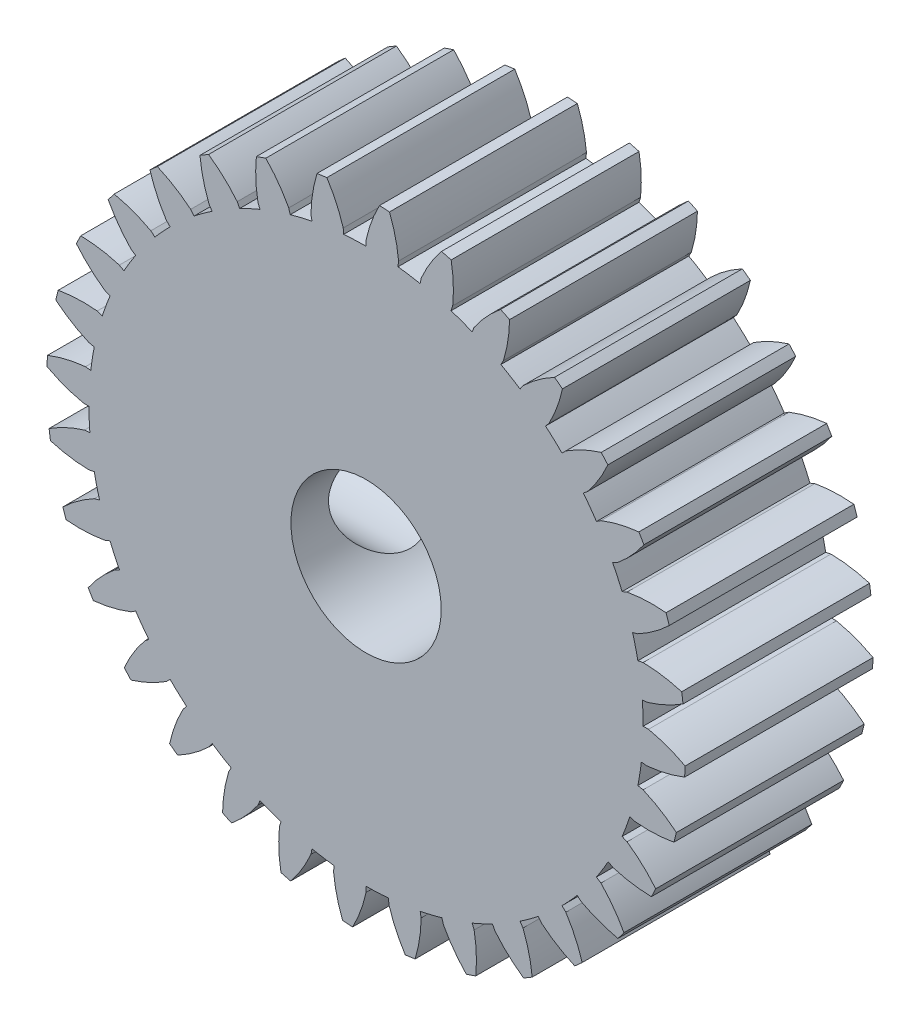
SolidWorks part; units mm, degrees
ref_plane "Front Plane" through (0, 0, 0) normal (0, 0, 1) x (1, 0, 0)
ref_plane "Top Plane" through (0, 0, 0) normal (0, 1, 0) x (1, 0, 0)
ref_plane "Right Plane" through (0, 0, 0) normal (1, 0, 0) x (0, 0, -1)
sketch "Gear" plane through (0, 0, 0) normal (0, 0, 1) x (1, 0, 0)
  circle A0 centre (0, 0) radius 8
  circle A1 centre (0, 0) radius 8.5
  circle A2 centre (0, 0) radius 7.375
  circle A3 centre (0, 0) radius 7.5
  circle A4 centre (0, 0) radius 7.5175
  dimension "Pitch" = 16
  dimension "Addendum" = 17
  dimension "Root" = 14.75
  dimension "Clearance" = 15
  dimension "Base" = 15.0351
sketch "Involute" plane through (0, 0, 0) normal (0, 0, 1) x (1, 0, 0)
  line L0 (0, 0) -> (0, 7.5175)
  line L1 (0, 0) -> (3.7588, 6.5104) construction
  line L2 (0, 0) -> (6.5104, 3.7588) construction
  line L3 (0, 0) -> (7.5175, 0) construction
  line L4 (7.5175, 0) -> (7.5175, 11.8085) construction
  line L5 (6.5104, 3.7588) -> (2.5742, 10.5764) construction
  line L6 (3.7588, 6.5104) -> (0.3499, 8.4785) construction
  line L7 (0, 0) -> (0.7841, 7.9615) construction
  line L8 (0, 0) -> (1.5607, 7.8463)
  line L9 (0.4614, 7.9867) -> (0, 0) construction
  circle A0 centre (0, 0) radius 7.5175 construction
  circle A1 centre (0, 0) radius 8 construction
  arc A3 (0.7841, 7.9615) -> (0.1378, 7.9988) centre (0, 0) ccw
  spline S0 degree 3 poles (0, 7.5175) (0.6613, 10.5961) (4.9807, 11.8125) (7.5175, 11.8085) knots 0 0 0 0 1 1 1 1
  spline S1 degree 3 poles (0.8656, 7.4675) (0.5632, 10.6018) (-3.5874, 12.3075) (-6.1078, 12.5956) knots 0 0 0 0 1 1 1 1
  point P10 (0, 0)
  dimension "Involute Control" = 90
  dimension "Base Circle Quarter Circumference" = 11.8085
  dimension "D1" = 7.8724
  dimension "D2" = 3.9362
  dimension "Circular Pitch" = 11.25
  dimension "Involute Array" = 4
sketch "Sketch3" plane through (0, 0, 0) normal (0, 0, 1) x (1, 0, 0)
  line L0 (0.8656, 7.4675) -> (0.8492, 7.3259)
  line L2 (0, 7.5175) -> (0, 7.375)
  arc A2 (0.3574, 8.4925) -> (0, 7.5175) centre (3.6484, 6.7332) ccw
  circle A10 centre (0, 0) radius 7.375 construction
  circle A11 centre (0, 0) radius 7.5175 construction
  arc A17 (0.8656, 7.4675) -> (0.6229, 8.4771) centre (-2.8488, 7.1085) ccw
  arc A18 (0.8492, 7.3259) -> (0, 7.375) centre (0, 0) ccw
  arc A19 (0.6229, 8.4771) -> (0.3574, 8.4925) centre (0, 0) ccw
  circle A20 centre (0, 0) radius 8.5 construction
  spline S1 degree 3 poles (0.8656, 7.4675) (0.5632, 10.6018) (-3.5874, 12.3075) (-6.1078, 12.5956) knots 0 0 0 0 1 1 1 1 construction
  spline S2 degree 3 poles (0, 7.5175) (0.6613, 10.5961) (4.9807, 11.8125) (7.5175, 11.8085) knots 0 0 0 0 1 1 1 1 construction
extrude "Boss-Extrude1" add sketch "Sketch3" along normal blind 5
ref_axis "Axis1" through (0, 0, 0) along (0, 0, 1)
pattern_circular "CirPattern1" count 32 over 360 about axis through (0, 0, 0) along (0, 0, 1) of bodies 101
sketch "Sketch6" plane through (0, 0, 0) normal (0, 0, 1) x (1, 0, 0)
  circle A0 centre (0, 0) radius 7.375 construction
  circle A1 centre (0, 0) radius 7.375
  circle A2 centre (0, 0) radius 2
  dimension "D1" = 4
extrude "Boss-Extrude3" add sketch "Sketch6" along normal up to surface (5 mm away) up to face at (-1.0773, 7.7198, 5)
sketch "Sketch9" plane through (0, 0, 0) normal (1, 0, 0) x (0, 0, -1)
  line L0 (-5, 8.4771) -> (0, 8.4771) construction
  circle A0 centre (-2.5, 0) radius 1.5
  point P8 (-2.5, 8.4771)
  dimension "D1" = 3
extrude "Cut-Extrude2" cut sketch "Sketch9" against normal blind 9
sketch "Sketch10" plane through (0, 0, 0) normal (1, 0, 0) x (0, 0, -1)
  line L0 (-5, 0) -> (0, 0) construction
  line L1 (-4, -1.5) -> (-1, -1.5)
  line L2 (-4, -1.5) -> (-4, 1.5)
  line L3 (-4, 1.5) -> (-1, 1.5)
  line L4 (-1, -1.5) -> (-1, 1.5)
  line L5 (-4, -1.5) -> (-1, 1.5) construction
  line L6 (-4, 1.5) -> (-1, -1.5) construction
  point P0 (-2.5, 0)
  dimension "D1" = 3
  dimension "D2" = 3
extrude "Cut-Extrude3" cut sketch "Sketch10" along direction (1, 0, 0) on the side of the normal up to surface (2.7792 mm away) from offset 10 up to face at (-7.1866, -1.6426, 2.4889) offset against normal yes
equation "\"Module\"= .5"
equation "\"Teeth\"= 32"
equation "\"Pressure Angle\"= 20deg"
equation "\"Pitch@Gear\"= \"Module\" * \"Teeth\""
equation "\"Addendum@Gear\" = \"Pitch@Gear\" +  ( \"Module\" * 2 ) "
equation "\"Clearance@Gear\" = \"Pitch@Gear\" - ( \"Module\" * 2 )"
equation "\"Root@Gear\"= \"Pitch@Gear\" - ( ( \"Module\" * 1.25 ) * 2 )"
equation "\"Base@Gear\"= \"Pitch@Gear\" * cos ( \"Pressure Angle\" )"
equation "\"Circular Pitch@Involute\"=360/\"Teeth\""
equation "\"Base Circle Quarter Circumference@Involute\"= \"Base@Gear\" * pi / 4"
equation "\"D1@Involute\"= \"Base Circle Quarter Circumference@Involute\" / 3 * 2"
equation "\"D2@Involute\"= \"Base Circle Quarter Circumference@Involute\" / 3"
equation "\"D1@CirPattern1\"= \"Teeth\""
